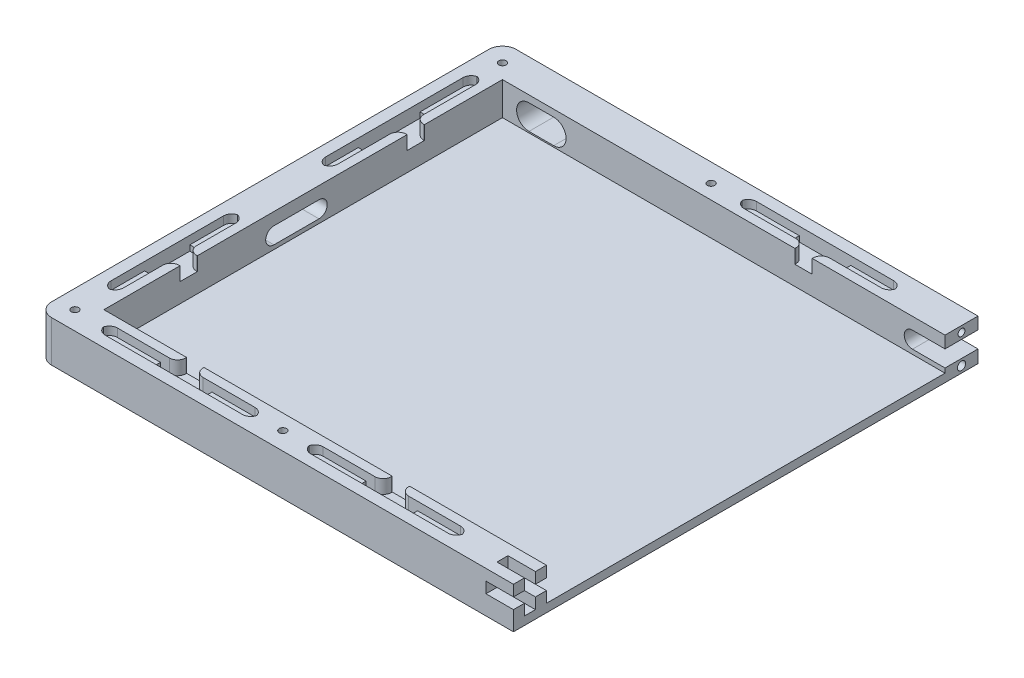
SolidWorks part; units mm, degrees
ref_plane "Front Plane" through (0, 0, 0) normal (0, 0, 1) x (1, 0, 0)
ref_plane "Top Plane" through (0, 0, 0) normal (0, 1, 0) x (1, 0, 0)
ref_plane "Right Plane" through (0, 0, 0) normal (1, 0, 0) x (0, 0, -1)
sketch "Sketch1" plane through (0, 0, 0) normal (0, 1, 0) x (1, 0, 0)
  line L0 (-185.215, 0) -> (43.0487, 0) construction
  line L1 (0, 72.5) -> (-161, 72.5)
  line L2 (0, 215.1028) -> (0, -153.2812) construction
  line L3 (-161, 72.5) -> (-161, -72.5)
  line L4 (-161, -72.5) -> (0, -72.5)
  line L5 (0, 72.5) -> (0, -72.5)
  point P9 (0, 0)
  dimension "D1" = 161
  dimension "D2" = 72.5
extrude "Boss-Extrude1" add sketch "Sketch1" along normal blind 3
sketch "Sketch2" plane through (0, 0, 0) normal (0, 1, 0) x (1, 0, 0)
  line L0 (-224.2217, 0) -> (91.1792, 0) construction
  line L1 (0, 149.3369) -> (0, -151.0656) construction
  line L2 (0, 72.5) -> (0, 84.5)
  line L3 (0, 84.5) -> (-173, 84.5)
  line L4 (-173, 84.5) -> (-173, -84.5)
  line L5 (-173, -84.5) -> (0, -84.5)
  line L6 (0, -84.5) -> (0, -72.5)
  line L8 (-161, 72.5) -> (-161, -72.5) construction
  line L13 (0, -72.5) -> (0, 72.5)
  line L14 (0, 72.5) -> (-161, 72.5)
  line L15 (-161, 72.5) -> (-161, -72.5)
  line L16 (-161, -72.5) -> (0, -72.5)
  line L18 (0, 72.5) -> (-161, 72.5)
  line L19 (-161, 72.5) -> (-161, -72.5)
  line L20 (-161, -72.5) -> (0, -72.5)
  dimension "D1" = 12
  dimension "D2" = 12
  dimension "D3" = 12
  dimension "D4" = 0
extrude "Boss-Extrude2" add sketch "Sketch2" along normal blind 15
sketch "Sketch3" plane through (0, 15, 0) normal (0, 1, 0) x (1, 0, 0)
  line L0 (-161, 72.5) -> (-161, 44.1) construction
  line L1 (-161, -72.5) -> (-161, 72.5) construction
  line L2 (-161, -72.5) -> (-161, -44.8) construction
  line L3 (-161, 44.1) -> (-161, 37.8)
  line L4 (-161, 44.1) -> (-164.3, 44.1)
  line L5 (-161, 37.8) -> (-164.3, 37.8)
  line L6 (-164.3, 44.1) -> (-164.3, 68.95)
  line L7 (-164.3, 37.8) -> (-164.3, 12.95)
  line L8 (-164.3, 68.95) -> (-168.8, 68.95)
  line L9 (-168.8, 68.95) -> (-168.8, 12.95)
  line L10 (-168.8, 12.95) -> (-164.3, 12.95)
  line L11 (-161, 72.5) -> (-161, -72.5) construction
  line L12 (-24.95, -75.8) -> (-49.8, -75.8)
  line L13 (-161, -38.5) -> (-161, -44.8)
  line L14 (-161, -38.5) -> (-164.3, -38.5)
  line L15 (-161, -44.8) -> (-164.3, -44.8)
  line L16 (-164.3, -38.5) -> (-164.3, -18.2)
  line L17 (-164.3, -18.2) -> (-168.8, -18.2)
  line L18 (-168.8, -18.2) -> (-168.8, -65.1)
  line L19 (-168.8, -65.1) -> (-164.3, -65.1)
  line L20 (-164.3, -65.1) -> (-164.3, -44.8)
  line L21 (-24.95, -80.3) -> (-24.95, -75.8)
  line L22 (-80.95, -80.3) -> (-24.95, -80.3)
  line L23 (-80.95, -75.8) -> (-80.95, -80.3)
  line L24 (-56.1, -75.8) -> (-80.95, -75.8)
  line L25 (-56.1, -72.5) -> (-56.1, -75.8)
  line L26 (-49.8, -72.5) -> (-56.1, -72.5)
  line L27 (-49.8, -75.8) -> (-49.8, -72.5)
  line L28 (-99.75, -80.3) -> (-99.75, -75.8)
  line L29 (-155.75, -80.3) -> (-99.75, -80.3)
  line L30 (-155.75, -75.8) -> (-155.75, -80.3)
  line L31 (-130.9, -75.8) -> (-155.75, -75.8)
  line L32 (-130.9, -72.5) -> (-130.9, -75.8)
  line L33 (-124.6, -72.5) -> (-130.9, -72.5)
  line L34 (-124.6, -75.8) -> (-124.6, -72.5)
  line L35 (-99.75, -75.8) -> (-124.6, -75.8)
  line L36 (0, -72.5) -> (-161, -72.5) construction
  line L37 (-161, -72.5) -> (0, -72.5) construction
  line L38 (-48.3, 75.8) -> (-48.3, 72.5)
  line L39 (-23.45, 75.8) -> (-48.3, 75.8)
  line L40 (-23.45, 80.3) -> (-23.45, 75.8)
  line L41 (-79.45, 80.3) -> (-23.45, 80.3)
  line L42 (-79.45, 75.8) -> (-79.45, 80.3)
  line L43 (-54.6, 75.8) -> (-79.45, 75.8)
  line L44 (-54.6, 72.5) -> (-54.6, 75.8)
  line L45 (-48.3, 72.5) -> (-54.6, 72.5)
  line L46 (-161, 72.5) -> (0, 72.5) construction
  dimension "D1" = 28.4
  dimension "D2" = 56
  dimension "D3" = 6.3
  dimension "D4" = 3.3
  dimension "D5" = 6.3
  dimension "D6" = 20.3
  dimension "D7" = 4.5
  dimension "D8" = 4.5
  dimension "D9" = 27.7
  dimension "D10" = 3.3
  dimension "D11" = 30.1
  dimension "D12" = 6.3
  dimension "D13" = 3.3
  dimension "D14" = 4.5
  dimension "D15" = 56
  dimension "D16" = 68.5
  dimension "D17" = 6.3
  dimension "D18" = 3.3
  dimension "D19" = 4.5
  dimension "D20" = 56
  dimension "D21" = 6.3
  dimension "D22" = 3.3
  dimension "D23" = 4.5
  dimension "D24" = 56
  dimension "D25" = 48.3
extrude "Cut-Extrude1" cut sketch "Sketch3" against normal blind 3
sketch "Sketch4" plane through (0, 12, 0) normal (0, 1, 0) x (1, 0, 0)
  line L1 (-54.6, 72.5) -> (-48.3, 72.5)
  line L2 (-48.3, 72.5) -> (-48.3, 75.8)
  line L3 (-48.3, 75.8) -> (-35.875, 75.8) construction
  line L4 (-130.9, -75.8) -> (-143.325, -75.8) construction
  line L5 (-54.6, 75.8) -> (-67.025, 75.8) construction
  line L6 (-79.45, 75.8) -> (-54.6, 75.8) construction
  line L7 (-48.3, 75.8) -> (-23.45, 75.8) construction
  line L10 (-54.6, 72.5) -> (-54.6, 75.8)
  line L14 (-48.3, 75.8) -> (-42.0875, 75.8)
  line L15 (-161, 44.1) -> (-161, 37.8)
  line L16 (-161, 37.8) -> (-164.3, 37.8)
  line L17 (-164.3, 44.1) -> (-164.3, 56.525) construction
  line L18 (-164.3, 44.1) -> (-164.3, 68.95) construction
  line L19 (-164.3, 37.8) -> (-164.3, 25.375) construction
  line L20 (-164.3, 12.95) -> (-164.3, 37.8) construction
  line L21 (-161, 44.1) -> (-164.3, 44.1)
  line L24 (-130.9, -75.8) -> (-155.75, -75.8) construction
  line L26 (-124.6, -75.8) -> (-112.175, -75.8) construction
  line L30 (-164.3, 44.1) -> (-164.3, 50.3125)
  line L31 (-164.3, 50.3125) -> (-168.8, 50.3125)
  line L32 (-168.8, 68.95) -> (-168.8, 12.95) construction
  line L33 (-168.8, 50.3125) -> (-168.8, 27.8502)
  line L34 (-168.8, 68.95) -> (-168.8, 12.95) construction
  line L35 (-168.8, 27.8502) -> (-164.3, 27.8502)
  line L36 (-164.3, 27.8502) -> (-164.3, 37.8)
  line L37 (-164.3, -38.5) -> (-164.3, -28.35) construction
  line L38 (-164.3, -38.5) -> (-164.3, -18.2) construction
  line L39 (-168.8, -33.425) -> (-168.8, -49.875)
  line L40 (-164.3, -65.1) -> (-164.3, -44.8) construction
  line L41 (-164.3, -33.425) -> (-168.8, -33.425)
  line L42 (-168.8, -18.2) -> (-168.8, -65.1) construction
  line L43 (-164.3, -44.8) -> (-164.3, -54.95) construction
  line L44 (-168.8, -49.875) -> (-164.3, -49.875)
  line L45 (-164.3, -49.875) -> (-164.3, -44.8)
  line L46 (-164.3, -44.8) -> (-161, -44.8)
  line L47 (-161, -44.8) -> (-161, -38.5)
  line L48 (-161, -38.5) -> (-164.3, -38.5)
  line L49 (-164.3, -38.5) -> (-164.3, -33.425)
  line L50 (-99.75, -75.8) -> (-124.6, -75.8) construction
  line L51 (-130.9, -72.5) -> (-130.9, -75.8)
  line L52 (-130.9, -75.8) -> (-137.1125, -75.8)
  line L53 (-137.1125, -75.8) -> (-137.1125, -80.3)
  line L54 (-155.75, -80.3) -> (-99.75, -80.3) construction
  line L55 (-137.1125, -80.3) -> (-118.3875, -80.3)
  line L56 (-118.3875, -80.3) -> (-118.3875, -75.8)
  line L59 (-124.6, -72.5) -> (-130.9, -72.5)
  line L60 (-124.6, -72.5) -> (-124.6, -75.8)
  line L61 (-124.6, -75.8) -> (-118.3875, -75.8)
  line L62 (-56.1, -75.8) -> (-68.525, -75.8) construction
  line L63 (-56.1, -75.8) -> (-80.95, -75.8) construction
  line L64 (-49.8, -75.8) -> (-37.375, -75.8) construction
  line L65 (-24.95, -75.8) -> (-49.8, -75.8) construction
  line L66 (-56.1, -75.8) -> (-62.3125, -75.8)
  line L67 (-62.3125, -75.8) -> (-62.3125, -80.3)
  line L68 (-80.95, -80.3) -> (-24.95, -80.3) construction
  line L69 (-62.3125, -80.3) -> (-43.5875, -80.3)
  line L70 (-43.5875, -80.3) -> (-43.5875, -75.8)
  line L71 (-43.5875, -75.8) -> (-49.8, -75.8)
  line L72 (-49.8, -75.8) -> (-49.8, -72.5)
  line L73 (-49.8, -72.5) -> (-56.1, -72.5)
  line L74 (-56.1, -72.5) -> (-56.1, -75.8)
  line L80 (-54.6, 75.8) -> (-60.8125, 75.8)
  line L81 (-60.8125, 75.8) -> (-60.8125, 80.3)
  line L82 (-23.45, 80.3) -> (-79.45, 80.3) construction
  line L83 (-60.8125, 80.3) -> (-42.0875, 80.3)
  line L84 (-23.45, 80.3) -> (-79.45, 80.3) construction
  line L85 (-42.0875, 80.3) -> (-42.0875, 75.8)
extrude "Cut-Extrude2" cut sketch "Sketch4" against normal blind 2
sketch "Sketch5" plane through (-173, 0, 0) normal (-1, 0, 0) x (0, 0, 1)
  line L0 (0, 7.5) -> (32.6582, 7.5) construction
  line L1 (-84.5, 7.5) -> (0, 7.5) construction
  line L2 (-84.5, 15) -> (-84.5, 0) construction
  line L3 (-84.5, 11.8257) -> (-8.75, 11.8257) construction
  line L4 (-5.75, 10.5) -> (10.63, 10.5)
  line L5 (-5.75, 4.5) -> (10.63, 4.5)
  line L8 (-8.75, 4.845) -> (-8.75, 10.155) construction
  arc A0 (-5.75, 4.5) -> (-5.75, 10.5) centre (-5.75, 7.5) cw
  arc A1 (10.63, 10.5) -> (10.63, 4.5) centre (10.63, 7.5) cw
  point P17 (-5.75, 10.5)
  point P21 (-8.75, 7.5)
  dimension "D2" = 3
  dimension "D1" = 16.38
  dimension "D3" = 75.75
extrude "Cut-Extrude3" cut sketch "Sketch5" against normal blind 12
sketch "Sketch7" plane through (0, 0, -84.5) normal (0, 0, -1) x (-1, 0, 0)
  line L0 (60.062, 7.6343) -> (-60.062, 7.6343) construction
  line L1 (0, 0) -> (173, 0) construction
  line L2 (14.8425, 7.6343) -> (14.8425, 12.6467) construction
  line L3 (-4.5375, 10.6343) -> (11.8425, 10.6343)
  line L4 (-4.5375, 4.6343) -> (11.8425, 4.6343)
  line L5 (0, 11.4722) -> (14.8425, 11.4722) construction
  line L6 (0, 15) -> (0, 0) construction
  arc A0 (-4.5375, 4.6343) -> (-4.5375, 10.6343) centre (-4.5375, 7.6343) cw
  arc A1 (11.8425, 10.6343) -> (11.8425, 4.6343) centre (11.8425, 7.6343) cw
  point P3 (0, 7.6343)
  dimension "D3" = 3
  dimension "D1" = 14.8425
  dimension "D2" = 16.38
  dimension "D4" = 7.6343
extrude "Cut-Extrude5" cut sketch "Sketch7" against normal blind 12
sketch "Sketch8" plane through (0, 0, -84.5) normal (0, 0, -1) x (-1, 0, 0)
  line L0 (142.36, 8) -> (151.36, 8) construction
  line L2 (173, 15) -> (173, 0) construction
  line L5 (142.36, 12.5) -> (151.36, 12.5)
  line L6 (142.36, 3.5) -> (151.36, 3.5)
  line L7 (0, 15) -> (173, 15) construction
  arc A0 (142.36, 3.5) -> (142.36, 12.5) centre (142.36, 8) cw
  arc A1 (151.36, 12.5) -> (151.36, 3.5) centre (151.36, 8) cw
  point P0 (146.86, 8)
  dimension "D5" = 9
  dimension "D1" = 26.14
  dimension "D2" = 7
  dimension "D4" = 9
extrude "Cut-Extrude6" cut sketch "Sketch8" against normal blind 20
sketch "Sketch10" plane through (0, 0, 0) normal (1, 0, 0) x (0, 0, -1)
  line L0 (-72.5, 3) -> (-72.5, 15) construction
  line L1 (-72.5, 15) -> (-84.5, 15) construction
  line L2 (-84.5, 15) -> (-84.5, 3) construction
  line L3 (-84.5, 15) -> (-84.5, 0) construction
  line L4 (-84.5, 3) -> (-72.5, 3) construction
  line L5 (-72.5, 3) -> (-84.5, 15) construction
  line L6 (-84.5, 15) -> (-72.5, 15) construction
  line L7 (-72.5, 15) -> (-84.5, 3) construction
  line L8 (-78.5, 15.3824) -> (-78.5, 3) construction
  line L9 (-84.5, 9) -> (-71.292, 9) construction
  line L10 (-80.5, 15) -> (-76.5, 15)
  line L11 (-72.5, 7) -> (-72.5, 11)
  line L12 (-76.5, 3) -> (-80.5, 3)
  line L13 (-84.5, 7) -> (-84.5, 11)
  line L14 (-80.5, 15) -> (-80.5, 11)
  line L15 (-80.5, 11) -> (-84.5, 11)
  line L16 (-84.5, 7) -> (-80.5, 7)
  line L17 (-80.5, 7) -> (-80.5, 3)
  line L18 (-76.5, 3) -> (-76.5, 7)
  line L19 (-76.5, 7) -> (-72.5, 7)
  line L20 (-72.5, 11) -> (-76.5, 11)
  line L21 (-76.5, 11) -> (-76.5, 15)
  line L22 (-78.5, 9) -> (-78.5, 15) construction
  line L23 (-72.5, 9) -> (-84.5, 9) construction
  point P15 (-78.5, 15)
  point P19 (-72.5, 9)
  point P22 (-78.5, 3)
  point P25 (-84.5, 9)
  dimension "D1" = 4
  dimension "D2" = 4
  dimension "D3" = 4
  dimension "D4" = 4
  dimension "D5" = 0
extrude "Cut-Extrude8" cut sketch "Sketch10" against normal blind 10
fillet "Fillet2" radius 5 1 edges at (-173, 7.5, 84.5)
fillet "Fillet3" radius 5 1 edges at (-173, 7.5, -84.5)
sketch "Sketch11" plane through (0, 0, 0) normal (1, 0, 0) x (0, 0, -1)
  line L0 (72.5, 4.6343) -> (84.5, 4.6343) construction
  line L1 (72.5, 4.6343) -> (72.5, 0) construction
  line L2 (-84.5, 0) -> (84.5, 0) construction
  line L3 (72.5, 0) -> (84.5, 0) construction
  line L4 (84.5, 0) -> (84.5, 4.6343) construction
  line L5 (78.5, 4.6343) -> (78.5, 0) construction
  line L6 (72.5, 2.3172) -> (84.5, 2.3172) construction
  line L7 (72.5, 15) -> (72.5, 10.6343) construction
  line L8 (72.5, 10.6343) -> (84.5, 10.6343) construction
  line L9 (84.5, 10.6343) -> (84.5, 15) construction
  line L10 (84.5, 15) -> (72.5, 15) construction
  line L11 (72.5, 15) -> (78.5, 15) construction
  line L12 (78.5, 15) -> (78.5, 10.6343) construction
  line L13 (78.5, 10.6343) -> (72.5, 10.6343) construction
  line L14 (72.5, 10.6343) -> (72.5, 12.8172) construction
  line L15 (72.5, 12.8172) -> (84.5, 12.8172) construction
  circle A0 centre (78.5, 2.3172) radius 1.5
  circle A1 centre (78.5, 12.8172) radius 1.25
  dimension "D1" = 3
  dimension "D2" = 2.5
extrude "Cut-Extrude9" cut sketch "Sketch11" against normal blind 10
sketch "Sketch12" plane through (0, 0, 0) normal (0, -1, 0) x (-1, 0, 0)
  circle A0 centre (166.2678, -77.7678) radius 1.325
  circle A1 centre (90.35, -78.05) radius 1.325
  circle A2 centre (-80.0525, -78.05) radius 1.325
  circle A3 centre (-164.8078, -77.7678) radius 1.325
  circle A4 centre (-164.8078, 77.7678) radius 1.325
  circle A5 centre (-80.0525, 78.05) radius 1.325
  circle A6 centre (90.35, 77.7678) radius 1.325
  circle A7 centre (166.2678, 77.7678) radius 1.325
  circle A9 centre (90.35, -78.05) radius 3
  circle A10 centre (-80.0525, -78.05) radius 3
  circle A11 centre (-164.8078, -77.7678) radius 3
  circle A12 centre (-164.8078, 77.7678) radius 3
  circle A13 centre (-80.0525, 78.05) radius 3
  circle A14 centre (90.35, 77.7678) radius 3
  circle A15 centre (166.2678, 77.7678) radius 3
  circle A16 centre (166.2678, -77.7678) radius 3
  dimension "D1" = 2.65
  dimension "D2" = 2.65
  dimension "D3" = 2.65
  dimension "D4" = 2.65
  dimension "D5" = 2.65
  dimension "D6" = 2.65
  dimension "D7" = 2.65
  dimension "D8" = 2.65
  dimension "D9" = 6
  dimension "D10" = 6
  dimension "D11" = 6
  dimension "D12" = 6
  dimension "D13" = 6
  dimension "D14" = 6
  dimension "D15" = 6
  dimension "D16" = 6
extrude "Cut-Extrude10" cut sketch "Sketch12" against normal blind 17 contours A0 | A1 | A2 | A3 | A4 | A5 | A6 | A7
sketch "Sketch13" plane through (0, 0, 0) normal (0, -1, 0) x (1, 0, 0)
  circle A0 centre (-166.2678, -77.7678) radius 3
  circle A1 centre (-90.35, -77.7678) radius 3
  circle A2 centre (-166.2678, 77.7678) radius 3
  circle A3 centre (-90.35, 78.05) radius 3
  dimension "D1" = 6
  dimension "D2" = 6
  dimension "D3" = 6
  dimension "D4" = 6
extrude "Cut-Extrude11" cut sketch "Sketch13" against normal blind 8
sketch "Sketch14" plane through (0, 0, 0) normal (0, -1, 0) x (-1, 0, 0)
  line L0 (168, -84.5) -> (0, -84.5) construction
  line L1 (173, 79.5) -> (173, -79.5) construction
  line L2 (0, 84.5) -> (168, 84.5) construction
  circle A0 centre (153, -64.5) radius 6.25
  circle A1 centre (153, 64.5) radius 6.25
  point P0 (153, -64.5)
  dimension "D3" = 12.5
  dimension "D4" = 12.5
  dimension "D1" = 20
  dimension "D2" = 20
  dimension "D5" = 20
  dimension "D6" = 20
extrude "Cut-Extrude12" cut sketch "Sketch14" against normal blind 1
fillet "Fillet5" radius 3 10 edges at (-164.3, 12.5, -44.1) (-164.3, 12.5, -37.8) (-164.3, 12.5, 44.8) (-164.3, 12.5, 38.5) (-130.9, 12.5, 75.8) (-124.6, 12.5, 75.8) (-56.1, 12.5, 75.8) (-49.8, 12.5, 75.8) (-54.6, 12.5, -75.8) (-48.3, 12.5, -75.8)
fillet "Fillet6" radius 3 20 edges at (-168.8, 13.5, -12.95) (-164.3, 13.5, -12.95) (-164.3, 13.5, -68.95) (-168.8, 13.5, -68.95) (-168.8, 13.5, 18.2) (-164.3, 13.5, 18.2) (-168.8, 13.5, 65.1) (-164.3, 13.5, 65.1) (-155.75, 13.5, 75.8) (-155.75, 13.5, 80.3) (-99.75, 13.5, 80.3) (-99.75, 13.5, 75.8) (-80.95, 13.5, 80.3) (-80.95, 13.5, 75.8) (-24.95, 13.5, 80.3) (-24.95, 13.5, 75.8) (-23.45, 13.5, -75.8) (-23.45, 13.5, -80.3) (-79.45, 13.5, -75.8) (-79.45, 13.5, -80.3)
